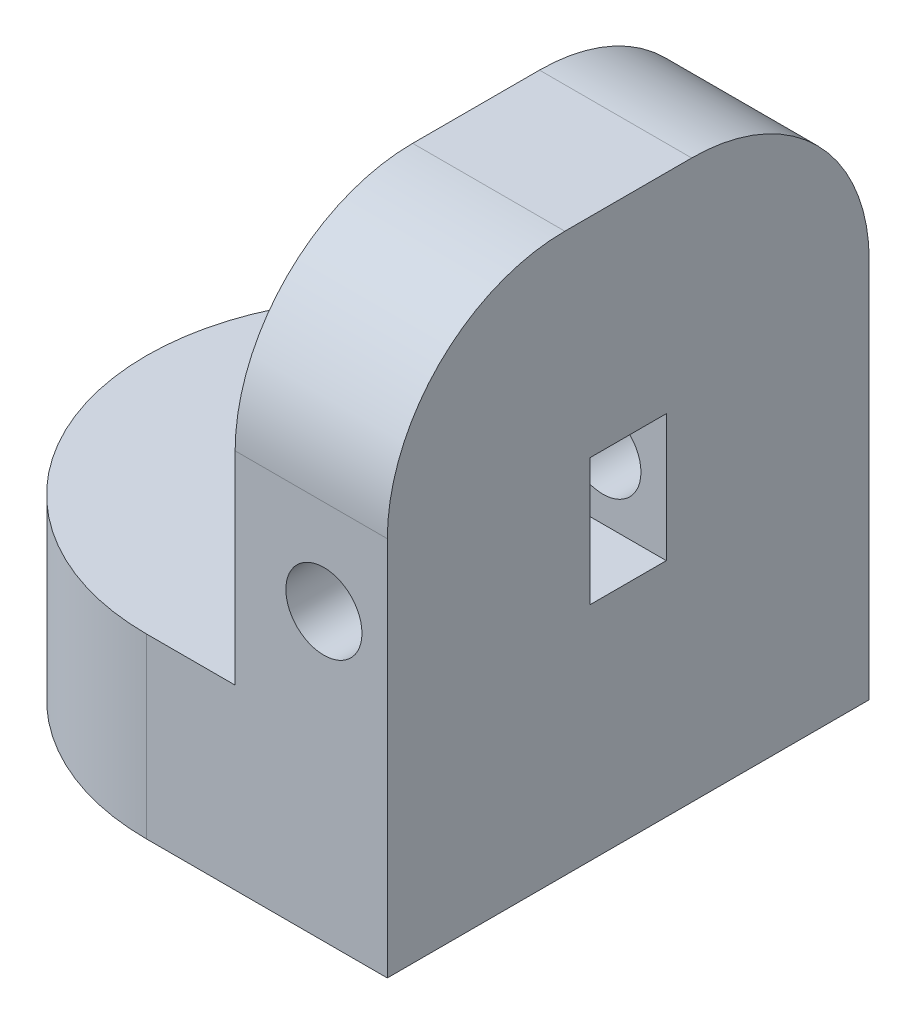
SolidWorks part; units mm, degrees
ref_plane "Front Plane" through (0, 0, 0) normal (0, 0, 1) x (1, 0, 0)
ref_plane "Top Plane" through (0, 0, 0) normal (0, 1, 0) x (1, 0, 0)
ref_plane "Right Plane" through (0, 0, 0) normal (1, 0, 0) x (0, 0, -1)
sketch "Sketch1" plane through (0, 0, 0) normal (0, 1, 0) x (1, 0, 0)
  line L5 (-9.5, 9.5) -> (9.5, 9.5)
  line L6 (-9.5, 9.5) -> (-9.5, -9.5)
  line L7 (-9.5, -9.5) -> (9.5, -9.5)
  line L8 (9.5, 9.5) -> (9.5, -9.5)
  line L9 (-9.5, 9.5) -> (9.5, -9.5) construction
  line L10 (-9.5, -9.5) -> (9.5, 9.5) construction
  point P0 (0, 0)
  dimension "D1" = 19
  dimension "D2" = 19
extrude "Boss-Extrude1" add sketch "Sketch1" along normal blind 7
fillet "Fillet1" radius 9.5 2 edges at (-9.5, 3.5, -9.5) (-9.5, 3.5, 9.5)
sketch "Sketch2" plane through (0, 7, 0) normal (0, 1, 0) x (1, 0, 0)
  line L0 (0, -9.5) -> (9.5, -9.5) construction
  line L1 (9.5, 9.5) -> (3.5, 9.5)
  line L2 (9.5, 9.5) -> (9.5, -9.5)
  line L3 (9.5, -9.5) -> (3.5, -9.5)
  line L4 (3.5, 9.5) -> (3.5, -9.5)
  dimension "D1" = 6
extrude "Boss-Extrude2" add sketch "Sketch2" along normal blind 15
fillet "Fillet2" radius 7 2 edges at (6.5, 22, -9.5) (6.5, 22, 9.5)
sketch "Sketch3" plane through (9.5, 0, 0) normal (1, 0, 0) x (0, 0, -1)
  line L0 (0, 0) -> (0, 22) construction
  line L1 (-9.5, 0) -> (9.5, 0) construction
  line L2 (-2.5, 22) -> (2.5, 22) construction
  line L4 (1.5, 13.77) -> (-1.5, 13.77)
  line L5 (-1.5, 13.77) -> (-1.5, 8.75)
  line L6 (-1.5, 8.75) -> (1.5, 8.75)
  line L7 (1.5, 13.77) -> (1.5, 8.75)
  point P11 (0, 8.75)
  point P12 (0, 13.77)
  dimension "D1" = 5.02
  dimension "D2" = 8.75
  dimension "D3" = 1.5
extrude "Cut-Extrude1" cut sketch "Sketch3" against normal through all
sketch "Sketch4" plane through (0, 0, -1.5) normal (0, 0, 1) x (1, 0, 0)
  line L1 (9.5, 15) -> (9.5, 0) construction
  line L2 (3.5, 13.77) -> (9.5, 13.77) construction
  circle A0 centre (7, 11.27) radius 1.5
  point P2 (0, 0)
  dimension "D1" = 3
  dimension "D2" = 2.5
  dimension "D3" = 2.5
extrude "Cut-Extrude2" cut sketch "Sketch4" against normal through all and the other way through all
sketch "Sketch5" plane through (0, 7, 0) normal (0, 1, 0) x (1, 0, 0)
  line L1 (3.5, 9.5) -> (-9.5, 9.5) construction
  line L2 (3.5, 9.5) -> (3.5, -9.5) construction
  line L3 (3.5, -9.5) -> (-9.5, -9.5) construction
  line L4 (-9.5, 9.5) -> (-9.5, -9.5) construction
  circle A0 centre (-2, 0) radius 2
  point P9 (-5.4809, 9.5)
  dimension "D3" = 4
  dimension "D1" = 13
  dimension "D2" = 19
  dimension "D4" = 7.5
  dimension "D5" = 9.5
extrude "Cut-Extrude3" cut sketch "Sketch5" against normal through all
